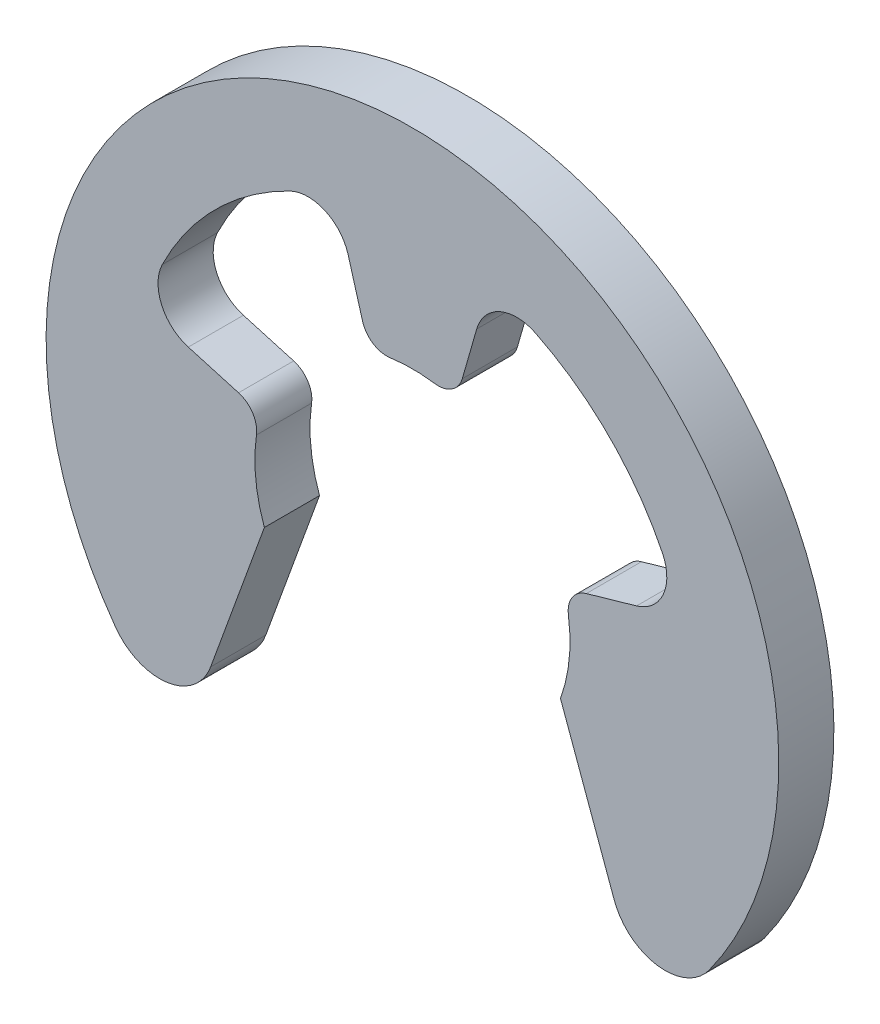
SolidWorks part; units mm, degrees
ref_plane "Plan de face" through (0, 0, 0) normal (0, 0, 1) x (1, 0, 0)
ref_plane "Plan de dessus" through (0, 0, 0) normal (0, 1, 0) x (1, 0, 0)
ref_plane "Plan de droite" through (0, 0, 0) normal (1, 0, 0) x (0, 0, -1)
ref_plane "Plan1" through (0, 0, 0.7) normal (0, 0, 1) x (1, 0, 0)
sketch "Esquisse1" plane through (0, 0, 0.7) normal (0, 0, 1) x (1, 0, 0)
  line L0 (0.6329, 2.2071) -> (0.8159, 2.8453)
  line L1 (2.8453, 0.8159) -> (2.2071, 0.6329)
  line L2 (1.8794, -0.684) -> (2.5614, -2.5579)
  line L3 (-2.5614, -2.5579) -> (-1.8794, -0.684)
  line L4 (-2.2071, 0.6329) -> (-2.8453, 0.8159)
  line L5 (-0.8159, 2.8453) -> (-0.6329, 2.2071)
  arc A0 (0.2823, 1.98) -> (0.6329, 2.2071) centre (0.3272, 2.2948) ccw
  arc A1 (0.8159, 2.8453) -> (1.5589, 3.1749) centre (1.3253, 2.6992) cw
  arc A2 (1.5589, 3.1749) -> (3.1749, 1.5589) centre (0, 0) cw
  arc A3 (3.1749, 1.5589) -> (2.8453, 0.8159) centre (2.6992, 1.3253) cw
  arc A4 (2.2071, 0.6329) -> (1.98, 0.2823) centre (2.2948, 0.3272) ccw
  arc A5 (1.98, 0.2823) -> (1.8794, -0.684) centre (0, 0) cw
  arc A6 (2.5614, -2.5579) -> (3.767, -2.7262) centre (3.2089, -2.3222) ccw
  arc A7 (3.767, -2.7262) -> (-3.767, -2.7262) centre (0, 0) ccw
  arc A8 (-3.767, -2.7262) -> (-2.5614, -2.5579) centre (-3.2089, -2.3222) ccw
  arc A9 (-1.8794, -0.684) -> (-1.98, 0.2823) centre (0, 0) cw
  arc A10 (-1.98, 0.2823) -> (-2.2071, 0.6329) centre (-2.2948, 0.3272) ccw
  arc A11 (-2.8453, 0.8159) -> (-3.1749, 1.5589) centre (-2.6992, 1.3253) cw
  arc A12 (-3.1749, 1.5589) -> (-1.5589, 3.1749) centre (0, 0) cw
  arc A13 (-1.5589, 3.1749) -> (-0.8159, 2.8453) centre (-1.3253, 2.6992) cw
  arc A14 (-0.6329, 2.2071) -> (-0.2823, 1.98) centre (-0.3272, 2.2948) ccw
  arc A15 (-0.2823, 1.98) -> (0.2823, 1.98) centre (0, 0) cw
extrude "Boss.-Extru.1" add sketch "Esquisse1" against normal blind 0.7
ref_axis "Axe1" through (0, 0, 0) along (0, 0, 1)
